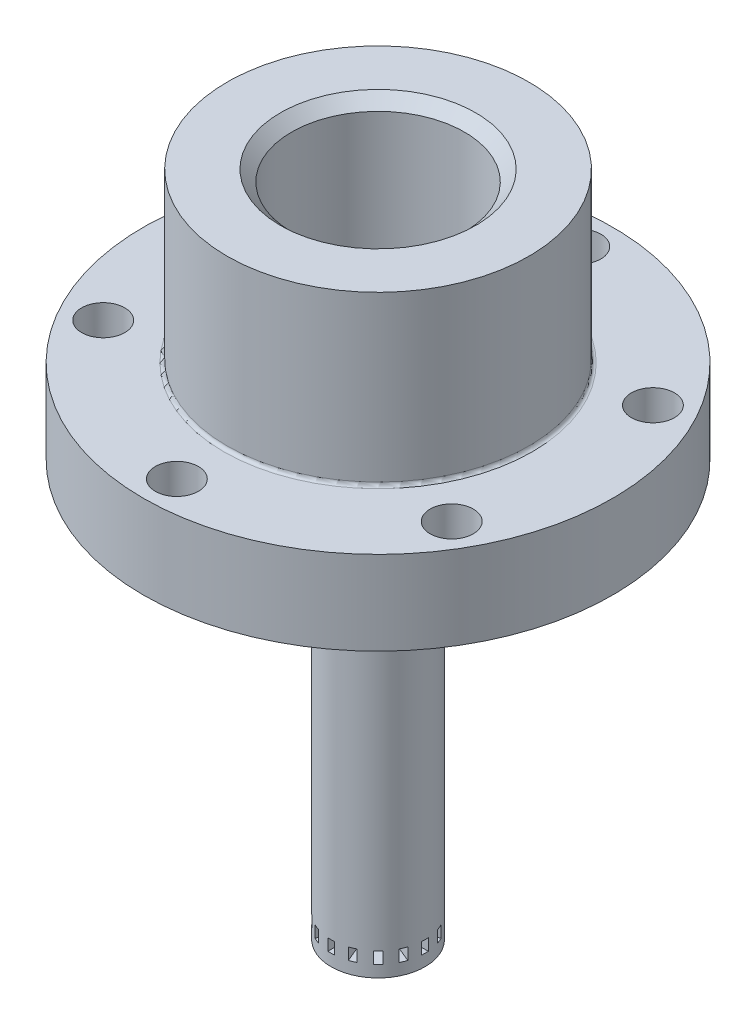
SolidWorks part; units mm, degrees
ref_plane "Front Plane" through (0, 0, 0) normal (0, 0, 1) x (1, 0, 0)
ref_plane "Top Plane" through (0, 0, 0) normal (0, 1, 0) x (1, 0, 0)
ref_plane "Right Plane" through (0, 0, 0) normal (1, 0, 0) x (0, 0, -1)
sketch "Sketch1" plane through (0, 0, 0) normal (0, 0, 1) x (1, 0, 0)
  line L0 (-3.556, -2.0672) -> (-1.524, -2.0672)
  line L1 (0, 8.2157) -> (0, -2.0672) construction
  line L2 (-3.556, 23.0788) -> (-1.524, 23.0788)
  line L3 (-3.556, -2.0672) -> (-3.556, 23.0788)
  line L7 (-1.524, 23.0788) -> (-1.524, -2.0672)
  dimension "D2" = 3.556
  dimension "D3" = 1.524
  dimension "D4" = 25.146
revolve "Revolve2" add sketch "Sketch1" angle 360 about L1 region at (-2.54, 10.5058, 0)
ref_plane "Plane1" through (-3.556, 0, 0) normal (-1, 0, 0) x (0, 0, 1)
sketch "Sketch2" plane through (-3.556, 0, 0) normal (-1, 0, 0) x (0, 0, 1)
  line L0 (0.2542, -1.1782) -> (-0.2538, -1.1782)
  line L1 (-0.2538, -1.1782) -> (-0.2538, -0.2892)
  line L2 (-0.2538, -0.2892) -> (0.2542, -0.2892)
  line L3 (0.2542, -0.2892) -> (0.2542, -1.1782)
  line L5 (-3.556, -2.0672) -> (3.556, -2.0672) construction
  line L6 (-3.556, -2.0672) -> (3.556, -2.0672)
  dimension "D2" = 0.508
  dimension "D1" = 0.889
  dimension "D3" = 0.889
extrude "Cut-Extrude1" cut sketch "Sketch2" against normal up to surface (2.0534 mm away) contours L1 L2 L3 L0 up to face at (0, -2.0672, 1.524)
ref_axis "Axis2" through (0, -2.0672, 0) along (0, 1, 0)
pattern_circular "CirPattern1" count 16 over 360 about axis through (0, -2.0672, 0) along (0, 1, 0) of "Cut-Extrude1"
ref_plane "Plane2" through (0, 23.0788, 0) normal (0, -1, 0) x (-1, 0, 0)
sketch "Sketch3" plane through (0, 23.0788, 0) normal (0, -1, 0) x (-1, 0, 0)
  circle A0 centre (0, 0) radius 1.524 construction
  circle A1 centre (0, 0) radius 3.556 construction
  circle A2 centre (0, 0) radius 1.524
  circle A3 centre (0, 0) radius 3.556
extrude "Boss-Extrude1" add sketch "Sketch3" against normal blind 6.35
ref_plane "Plane3" through (0, 29.4288, 0) normal (0, 1, 0) x (1, 0, 0)
sketch "Sketch4" plane through (0, 29.4288, 0) normal (0, 1, 0) x (1, 0, 0)
  circle A0 centre (0, 0) radius 17.78
  circle A1 centre (0, 0) radius 1.524
  dimension "D2" = 17.78
extrude "Boss-Extrude2" add sketch "Sketch4" along normal blind 6.35
sketch "Sketch11" plane through (0, 35.7788, 0) normal (0, 1, 0) x (1, 0, 0)
  line L0 (0, 0) -> (0, -15.24) construction
  circle A0 centre (0, -15.24) radius 1.6319
  circle A1 centre (0, 0) radius 15.24 construction
  dimension "D2" = 3.2639
extrude "Cut-Extrude2" cut sketch "Sketch11" against normal up to next
ref_axis "Axis1" through (0, -2.0672, 0) along (0, 1, 0)
pattern_circular "CirPattern2" count 6 over 360 about axis through (0, -2.0672, 0) along (0, 1, 0) of "Cut-Extrude2"
chamfer "Chamfer1" distance 3.048 angle 60 1 edges at (0, 35.7788, 1.524) first distance on face at (-14.6115, 35.7788, 8.436)
sketch "Sketch13" plane through (0, 35.7788, 0) normal (0, 1, 0) x (1, 0, 0)
  circle A0 centre (0, 0) radius 6.5481
  circle A1 centre (0, 0) radius 11.43
extrude "Boss-Extrude4" add sketch "Sketch13" along normal blind 12.7
fillet "Fillet4" radius 0.254 1 edges at (0, 35.7788, 11.43)
chamfer "Chamfer2" distance 0.8517 distance2 0.8395 1 edges at (0, 48.4788, 6.5481) first distance on face at (0, 48.4788, 11.43)
sketch "Sketch14" plane through (0, 35.7788, 0) normal (0, 1, 0) x (1, 0, 0)
  circle A0 centre (-13.1982, -7.62) radius 2.794
sketch "Sketch15" plane through (0, 29.4288, 0) normal (0, 1, 0) x (1, 0, 0)
  circle A0 centre (0, 0) radius 3.556
  circle A1 centre (0, 0) radius 4.699
extrude "Boss-Extrude5" add sketch "Sketch15" against normal blind 6.35
equation "\"ManifoldThickness\"= 0.250"
equation "\"D1@Boss-Extrude1\"=\"ManifoldThickness\""
equation "\"SkipDistance\"= \"OD\"'equal to pintle OD"
equation "\"OD\"= 0.280"
equation "\"AnnulusLength\"= 0.29"
equation "\"ManifoldChamberThickness\"= 0.35"
equation "\"D4@Sketch1\"=\"SkipDistance\"+\"AnnulusLength\"+\"ManifoldChamberThickness\"+\"HoleHeight\"+\"WeldHeight\""
equation "\"HoleHeight\"= 0.035"
equation "\"D2@Sketch1\"=\"OD\"/2"
equation "\"IR\"=0.06"
equation "\"D3@Sketch1\" = \"IR\""
equation "\"ID\"= \"IR\" * 2"
equation "\"440loose\"= 0.1285"
equation "\"D2@Sketch11\"=\"440loose\""
equation "\"ManifoldPlateThickness\"= 0.25"
equation "\"WeldHeight\"=0.035"
equation "\"D1@Sketch2\"=\"HoleHeight\""
equation "\"D3@Sketch2\"=\"WeldHeight\""
